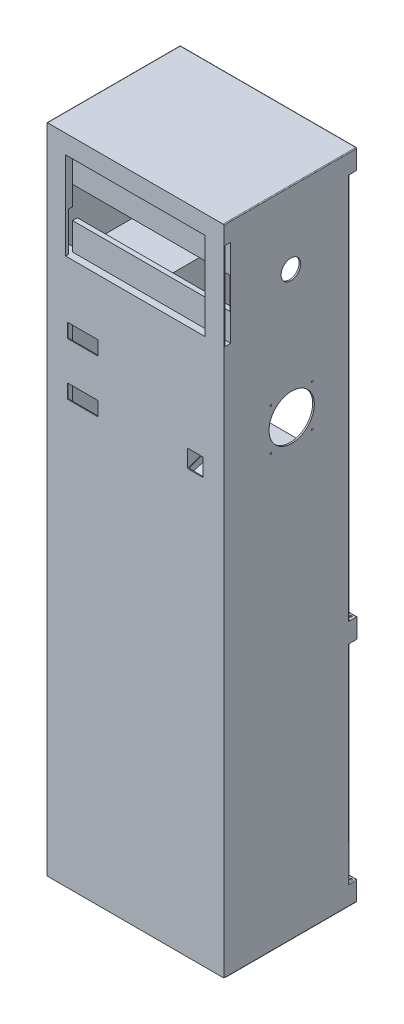
SolidWorks part; units mm, degrees
ref_plane "Front Plane" through (0, 0, 0) normal (0, 0, 1) x (1, 0, 0)
ref_plane "Top Plane" through (0, 0, 0) normal (0, 1, 0) x (1, 0, 0)
ref_plane "Right Plane" through (0, 0, 0) normal (1, 0, 0) x (0, 0, -1)
sketch "Sketch1" plane through (0, 0, 0) normal (0, 1, 0) x (1, 0, 0)
  line L1 (-225.5, 167.5) -> (225.5, 167.5)
  line L2 (-225.5, 167.5) -> (-225.5, -167.5)
  line L3 (-225.5, -167.5) -> (225.5, -167.5)
  line L4 (225.5, 167.5) -> (225.5, -167.5)
  line L5 (-225.5, 167.5) -> (225.5, -167.5) construction
  line L6 (-225.5, -167.5) -> (225.5, 167.5) construction
  point P0 (0, 0)
  dimension "D1" = 451
  dimension "D2" = 335
extrude "Boss-Extrude2" add sketch "Sketch1" along normal blind 1346
sketch "Sketch3" plane through (0, 0, -167.5) normal (0, 0, -1) x (-1, 0, 0)
  line L0 (225.5, 50) -> (225.5, 580)
  line L1 (225.5, 1346) -> (225.5, 0) construction
  line L2 (-225.5, 0) -> (225.5, 0) construction
  line L3 (225.5, 50) -> (-225.5, 50)
  line L4 (-225.5, 1346) -> (-225.5, 0) construction
  line L5 (-225.5, 50) -> (-225.5, 580)
  line L6 (-225.5, 580) -> (225.5, 580)
  line L7 (-225.5, 1346) -> (225.5, 1346) construction
  line L8 (225.5, 630) -> (-225.5, 630)
  line L9 (225.5, 630) -> (225.5, 1296)
  line L10 (225.5, 1296) -> (-225.5, 1296)
  line L11 (-225.5, 630) -> (-225.5, 1296)
  dimension "D1" = 530
  dimension "D2" = 50
  dimension "D3" = 50
  dimension "D4" = 50
fillet "Fillet1" radius 2 1 edges at (0, 0, -167.5)
sketch "Sketch6" plane through (0, 0, 167.5) normal (0, 0, 1) x (1, 0, 0)
  line L1 (-225.5, 1346) -> (225.5, 1346)
  line L2 (-225.5, 1346) -> (-225.5, 2)
  line L3 (-225.5, 2) -> (225.5, 2)
  line L4 (225.5, 1346) -> (225.5, 2)
extrude "Boss-Extrude3" add sketch "Sketch6" along normal blind 5
extrude "Cut-Extrude2" cut sketch "Sketch3" against normal blind 20
sketch "Sketch9" plane through (0, 0, -147.5) normal (0, 0, -1) x (-1, 0, 0)
  line L0 (-225.5, 50) -> (225.5, 50) construction
  line L1 (225.5, 580) -> (-225.5, 580) construction
  line L2 (-196.5, 50) -> (196.5, 50)
  line L3 (-196.5, 50) -> (-196.5, 580)
  line L4 (-196.5, 580) -> (196.5, 580)
  line L5 (196.5, 50) -> (196.5, 580)
  line L6 (-225.5, 580) -> (-225.5, 50) construction
  line L7 (225.5, 50) -> (225.5, 580) construction
  dimension "D1" = 29
  dimension "D2" = 29
sketch "Sketch10" plane through (0, 0, -147.5) normal (0, 0, -1) x (-1, 0, 0)
  line L0 (-225.5, 630) -> (225.5, 630) construction
  line L1 (-196.5, 630) -> (196.5, 630)
  line L2 (-196.5, 630) -> (-196.5, 1296)
  line L3 (-196.5, 1296) -> (196.5, 1296)
  line L4 (196.5, 630) -> (196.5, 1296)
  line L5 (225.5, 1296) -> (-225.5, 1296) construction
  line L6 (225.5, 630) -> (225.5, 1296) construction
  line L7 (-225.5, 1296) -> (-225.5, 630) construction
  dimension "D1" = 29
  dimension "D2" = 29
extrude "Cut-Extrude3" cut sketch "Sketch10" against normal blind 15
sketch "Sketch11" plane through (0, 0, -132.5) normal (0, 0, -1) x (-1, 0, 0)
  line L6 (68.5, 710) -> (-196.5, 710)
  line L15 (-196.5, 710) -> (-196.5, 964)
  line L16 (68.5, 710) -> (68.5, 964)
  line L17 (68.5, 964) -> (-196.5, 964)
  line L18 (-196.5, 1296) -> (-196.5, 981)
  line L19 (51.5, 1296) -> (-196.5, 1296)
  line L20 (51.5, 1296) -> (51.5, 981)
  line L21 (51.5, 981) -> (-196.5, 981)
  line L22 (68.5, 981) -> (196.5, 981)
  line L23 (196.5, 1296) -> (196.5, 981)
  line L24 (68.5, 1296) -> (68.5, 981)
  line L25 (68.5, 1296) -> (196.5, 1296)
  line L26 (-225.5, 630) -> (225.5, 630) construction
extrude "Cut-Extrude9" cut sketch "Sketch11" against normal blind 272
sketch "Sketch23" plane through (0, 981, 0) normal (0, 1, 0) x (1, 0, 0)
  line L0 (-68.5, -139.5) -> (-68.5, 132.5) construction
  line L1 (-68.5, 115.5) -> (-196.5, 115.5)
  line L2 (-68.5, 115.5) -> (-68.5, 112.5)
  line L3 (-68.5, 112.5) -> (-196.5, 112.5)
  line L4 (-196.5, 115.5) -> (-196.5, 112.5)
  line L5 (-196.5, -139.5) -> (-196.5, 132.5) construction
  line L6 (-68.5, 132.5) -> (-196.5, 132.5) construction
  line L7 (-51.5, -139.5) -> (-51.5, 132.5) construction
  line L8 (-51.5, 115.5) -> (196.5, 115.5)
  line L9 (-51.5, 115.5) -> (-51.5, 112.5)
  line L10 (-51.5, 112.5) -> (196.5, 112.5)
  line L11 (196.5, 115.5) -> (196.5, 112.5)
  line L12 (196.5, -139.5) -> (196.5, 132.5) construction
  line L13 (196.5, 132.5) -> (-51.5, 132.5) construction
  dimension "D1" = 17
  dimension "D2" = 3
  dimension "D3" = 3
  dimension "D4" = 17
extrude "Boss-Extrude4" add sketch "Sketch23" along normal blind 17
sketch "Sketch24" plane through (0, 1296, 0) normal (0, -1, 0) x (1, 0, 0)
  line L0 (-51.5, 139.5) -> (-51.5, -132.5) construction
  line L1 (-51.5, -115.5) -> (196.5, -115.5)
  line L2 (-51.5, -115.5) -> (-51.5, -112.5)
  line L3 (-51.5, -112.5) -> (196.5, -112.5)
  line L4 (196.5, -115.5) -> (196.5, -112.5)
  line L5 (196.5, 139.5) -> (196.5, -147.5) construction
  line L6 (-68.5, 139.5) -> (-68.5, -132.5) construction
  line L7 (-68.5, -115.5) -> (-196.5, -115.5)
  line L8 (-68.5, -115.5) -> (-68.5, -112.5)
  line L9 (-68.5, -112.5) -> (-196.5, -112.5)
  line L10 (-196.5, -115.5) -> (-196.5, -112.5)
  line L11 (-196.5, 139.5) -> (-196.5, -147.5) construction
  dimension "D1" = 17
  dimension "D2" = 3
  dimension "D3" = 17
  dimension "D4" = 3
extrude "Boss-Extrude5" add sketch "Sketch24" along normal blind 17
extrude "Cut-Extrude10" cut sketch "Sketch9" against normal blind 287
sketch "Sketch26" plane through (0, 981, 0) normal (0, 1, 0) x (1, 0, 0)
  line L1 (-196.5, 112.5) -> (-68.5, 112.5) construction
  line L2 (-196.5, -139.5) -> (-85.5, -139.5)
  line L3 (-196.5, -139.5) -> (-196.5, 112.5)
  line L4 (-196.5, 112.5) -> (-85.5, 112.5)
  line L5 (-85.5, -139.5) -> (-85.5, 112.5)
  line L6 (-68.5, -139.5) -> (-68.5, 112.5) construction
  dimension "D1" = 0
  dimension "D2" = 17
extrude "Cut-Extrude11" cut sketch "Sketch26" against normal up to surface (401 mm away) up to face at (0, 580, -80.75)
sketch "Sketch29" plane through (-196.5, 0, 0) normal (1, 0, 0) x (0, 0, -1)
  line L0 (112.5, 998) -> (112.5, 580) construction
  line L1 (-139.5, 1296) -> (112.5, 1296)
  line L2 (-139.5, 1296) -> (-139.5, 580)
  line L3 (-139.5, 580) -> (112.5, 580)
  line L4 (112.5, 1296) -> (112.5, 580)
  dimension "D1" = 0
extrude "Cut-Extrude12" cut sketch "Sketch29" against normal blind 27
sketch "Sketch33" plane through (0, 1296, 0) normal (0, -1, 0) x (1, 0, 0)
  line L1 (-223.5, 139.5) -> (-68.5, 139.5)
  line L2 (-223.5, 139.5) -> (-223.5, -112.5)
  line L3 (-223.5, -112.5) -> (-68.5, -112.5)
  line L4 (-68.5, 139.5) -> (-68.5, -112.5)
  dimension "D1" = 0
extrude "Cut-Extrude13" cut sketch "Sketch33" against normal blind 48
sketch "Sketch36" plane through (0, 0, 139.5) normal (0, 0, -1) x (-1, 0, 0)
  line L1 (-196.5, 1296) -> (51.5, 1296)
  line L2 (-196.5, 1296) -> (-196.5, 981)
  line L3 (-196.5, 981) -> (51.5, 981)
  line L4 (51.5, 1296) -> (51.5, 981)
extrude "Cut-Extrude14" cut sketch "Sketch36" against normal blind 31
sketch "Sketch39" plane through (0, 0, 139.5) normal (0, 0, -1) x (-1, 0, 0)
  line L0 (223.5, 1344) -> (223.5, 580) construction
  line L1 (68.5, 1344) -> (223.5, 1344)
  line L2 (68.5, 1344) -> (68.5, 981)
  line L3 (68.5, 981) -> (223.5, 981)
  line L4 (223.5, 1344) -> (223.5, 981)
  line L5 (68.5, 981) -> (85.5, 981) construction
  line L7 (223.5, 981) -> (85.5, 981)
  line L8 (223.5, 981) -> (223.5, 580)
  line L9 (223.5, 580) -> (85.5, 580)
  line L10 (85.5, 981) -> (85.5, 580)
  line M1 (223.5, 580) -> (223.5, 1344)
  line M2 (223.5, 1344) -> (68.5, 1344)
  line M3 (68.5, 1344) -> (68.5, 981)
  line M4 (68.5, 981) -> (85.5, 981)
  line M5 (85.5, 981) -> (85.5, 580)
  line M10 (196.5, 580) -> (223.5, 580)
  dimension "D1" = 0
extrude "Cut-Extrude15" cut sketch "Sketch39" against normal blind 31 contours L9 L3 M10 M1 M5 | L3 M4 M1 M2 M3
sketch "Sketch41" plane through (0, 0, 139.5) normal (0, 0, -1) x (-1, 0, 0)
  line L1 (-196.5, 964) -> (68.5, 964)
  line L2 (-196.5, 964) -> (-196.5, 710)
  line L3 (-196.5, 710) -> (68.5, 710)
  line L4 (68.5, 964) -> (68.5, 710)
extrude "Cut-Extrude16" cut sketch "Sketch41" against normal blind 31
sketch "Sketch43" plane through (0, 0, 170.5) normal (0, 0, -1) x (-1, 0, 0)
  line L0 (68.5, 1344) -> (68.5, 981) construction
  line L1 (81.5, 1294) -> (186.5, 1294)
  line L2 (81.5, 1294) -> (81.5, 1014)
  line L3 (81.5, 1014) -> (186.5, 1014)
  line L4 (186.5, 1294) -> (186.5, 1014)
  line L5 (223.5, 1344) -> (68.5, 1344) construction
  dimension "D1" = 13
  dimension "D2" = 50
  dimension "D3" = 105
  dimension "D4" = 280
extrude "Boss-Extrude6" add sketch "Sketch43" along normal blind 13.5
sketch "Sketch44" plane through (0, 0, 157) normal (0, 0, -1) x (-1, 0, 0)
  line L0 (186.5, 1294) -> (81.5, 1294) construction
  line L1 (92, 1280.25) -> (176, 1280.25)
  line L2 (92, 1280.25) -> (92, 1173.75)
  line L3 (92, 1173.75) -> (176, 1173.75)
  line L4 (176, 1280.25) -> (176, 1173.75)
  line L5 (92, 1146.25) -> (176, 1146.25)
  line L6 (186.5, 1014) -> (186.5, 1294) construction
  line L7 (81.5, 1160) -> (186.5, 1160)
  line L8 (81.5, 1294) -> (81.5, 1014) construction
  line L9 (186.5, 1014) -> (186.5, 1294) construction
  line L10 (176, 1039.75) -> (176, 1146.25)
  line L11 (92, 1039.75) -> (176, 1039.75)
  line L12 (92, 1039.75) -> (92, 1146.25)
  point P8 (134, 1173.75)
  dimension "D1" = 84
  dimension "D2" = 106.5
  dimension "D3" = 13.75
  dimension "D4" = 52.5
  dimension "D5" = 13.75
extrude "Cut-Extrude17" cut sketch "Sketch44" against normal blind 13.5 contours L4 L1 L2 L3 | L12 L11 L10 L5
sketch "Sketch46" plane through (0, 0, 139.5) normal (0, 0, -1) x (-1, 0, 0)
  line L5 (-196.5, 580) -> (196.5, 580)
  line L6 (-196.5, 580) -> (-196.5, 50)
  line L7 (-196.5, 50) -> (196.5, 50)
  line L8 (196.5, 580) -> (196.5, 50)
extrude "Cut-Extrude18" cut sketch "Sketch46" against normal blind 31
sketch "Sketch48" plane through (-196.5, 0, 0) normal (1, 0, 0) x (0, 0, -1)
  line L0 (-170.5, 50) -> (147.5, 50) construction
  line L1 (-170.5, 580) -> (112.5, 580)
  line L2 (-170.5, 580) -> (-170.5, 547)
  line L3 (-170.5, 547) -> (112.5, 547)
  line L4 (112.5, 580) -> (112.5, 547)
  dimension "D1" = 497
extrude "Boss-Extrude9" add sketch "Sketch48" along normal blind 31 separate body contours L2 L1 L4 L3
chamfer "Chamfer1" distance 30 angle 45 1 edges at (-165.5, 580, 29)
sketch "Sketch55" plane through (0, 50, 0) normal (0, 1, 0) x (1, 0, 0)
  line L1 (196.5, -170.5) -> (126.5, -170.5)
  line L2 (196.5, -170.5) -> (196.5, 147.5)
  line L3 (196.5, 147.5) -> (126.5, 147.5)
  line L4 (126.5, -170.5) -> (126.5, 147.5)
  line L5 (0, 95.2537) -> (0, -34.731)
  line L6 (-196.5, 147.5) -> (-126.5, 147.5)
  line L7 (-126.5, -170.5) -> (-126.5, 147.5)
  line L8 (-196.5, -170.5) -> (-126.5, -170.5)
  line L9 (-196.5, -170.5) -> (-196.5, 147.5)
  line M12 (-196.5, 147.5) -> (-196.5, -170.5)
  line M13 (-196.5, -170.5) -> (196.5, -170.5)
  line M14 (196.5, -170.5) -> (196.5, 147.5)
  dimension "D1" = 70
extrude "Cut-Extrude19" cut sketch "Sketch55" against normal blind 35 contours L7 L6 M13 M12 | L4 L3 M13 M14
sketch "Sketch56" plane through (0, 15, 0) normal (0, 1, 0) x (1, 0, 0)
  line L0 (-126.5, -170.5) -> (-126.5, 147.5) construction
  line L1 (0, -25.1133) -> (0, -98.0169)
  circle A0 centre (-161.5, 0) radius 17.5
  circle A1 centre (161.5, 0) radius 17.5
  dimension "D1" = 35
extrude "Cut-Extrude20" cut sketch "Sketch56" against normal blind 10 contours A0 | A1
sketch "Sketch57" plane through (0, 5, 0) normal (0, 1, 0) x (1, 0, 0)
  line L0 (0, 0) -> (0, 42.7914)
  circle A0 centre (161.5, 0) radius 4
  circle A1 centre (-161.5, 0) radius 4
  dimension "D1" = 8
extrude "Cut-Extrude21" cut sketch "Sketch57" against normal through all contours A0 | A1
sketch "Sketch58" plane through (0, 1346, 0) normal (0, 1, 0) x (1, 0, 0)
  line L1 (-225.5, 167.5) -> (225.5, 167.5)
  line L2 (-225.5, 167.5) -> (-225.5, -172.5)
  line L3 (-225.5, -172.5) -> (225.5, -172.5)
  line L4 (225.5, 167.5) -> (225.5, -172.5)
extrude "Boss-Extrude10" add sketch "Sketch58" along normal blind 319
sketch "Sketch59" plane through (0, 0, 172.5) normal (0, 0, 1) x (1, 0, 0)
  line L1 (-177.7, 1617.2) -> (177.7, 1617.2)
  line L2 (-177.7, 1617.2) -> (-177.7, 1393.8)
  line L3 (-177.7, 1393.8) -> (177.7, 1393.8)
  line L4 (177.7, 1617.2) -> (177.7, 1393.8)
  line L9 (-225.5, 1665) -> (225.5, 1665) construction
  line L10 (225.5, 2) -> (225.5, 1665) construction
  line L11 (-225.5, 1665) -> (-225.5, 2) construction
  dimension "D1" = 47.8
  dimension "D2" = 47.8
  dimension "D3" = 47.8
  dimension "D4" = 223.4
extrude "Cut-Extrude22" cut sketch "Sketch59" against normal blind 17.7
sketch "Sketch60" plane through (177.7, 0, 0) normal (-1, 0, 0) x (0, 0, 1)
  line L0 (154.8, 1393.8) -> (172.5, 1393.8) construction
  line L1 (154.8, 1617.2) -> (169.6, 1617.2)
  line L2 (154.8, 1617.2) -> (154.8, 1393.8)
  line L3 (154.8, 1393.8) -> (169.6, 1393.8)
  line L4 (169.6, 1617.2) -> (169.6, 1393.8)
  dimension "D1" = 14.8
extrude "Cut-Extrude23" cut sketch "Sketch60" against normal up to surface (47.8 mm away) up to face at (225.5, 563.1724, -72.0609)
sketch "Sketch61" plane through (0, 1296, 0) normal (0, -1, 0) x (1, 0, 0)
  line L0 (-225.5, -147.5) -> (-225.5, -167.5) construction
  line L2 (-225.5, -167.5) -> (225.5, -167.5) construction
  circle A0 centre (-217.5, -159.5) radius 2.5
  dimension "D1" = 5
  dimension "D2" = 8
  dimension "D3" = 8
extrude "Cut-Extrude24" cut sketch "Sketch61" against normal blind 10
sketch "Sketch62" plane through (0, 630, 0) normal (0, 1, 0) x (1, 0, 0)
  line L0 (225.5, 167.5) -> (-225.5, 167.5) construction
  line L1 (-225.5, 147.5) -> (-225.5, 167.5) construction
  circle A0 centre (-217.5, 159.5) radius 3.4591
  dimension "D1" = 8
  dimension "D2" = 8
sketch "Sketch63" plane through (0, 580, 0) normal (0, -1, 0) x (1, 0, 0)
  line L0 (-225.5, -147.5) -> (-225.5, -167.5) construction
  line L1 (-225.5, -167.5) -> (225.5, -167.5) construction
  circle A0 centre (-217.5, -159.5) radius 2.5
  dimension "D1" = 5
  dimension "D2" = 8
  dimension "D3" = 8
sketch "Sketch64" plane through (0, 50, 0) normal (0, 1, 0) x (1, 0, 0)
  line L0 (225.5, 167.5) -> (-225.5, 167.5) construction
  line L1 (-225.5, 147.5) -> (-225.5, 167.5) construction
  circle A0 centre (-217.5, 159.5) radius 2.5
  dimension "D1" = 5
  dimension "D2" = 8
  dimension "D3" = 8
sketch "Sketch66" plane through (0, 0, 170.5) normal (0, 0, -1) x (-1, 0, 0)
  line L0 (176, 1280.25) -> (176, 1173.75) construction
  line L1 (95, 1250.25) -> (173, 1250.25)
  line L2 (95, 1250.25) -> (95, 1214.25)
  line L3 (95, 1214.25) -> (173, 1214.25)
  line L4 (173, 1250.25) -> (173, 1214.25)
  line L5 (92, 1280.25) -> (92, 1173.75) construction
  line L6 (92, 1280.25) -> (176, 1280.25) construction
  line L7 (92, 1173.75) -> (176, 1173.75) construction
  line L8 (95, 1116.25) -> (95, 1080.25)
  line L9 (173, 1116.25) -> (173, 1080.25)
  line L10 (95, 1080.25) -> (173, 1080.25)
  line L11 (95, 1116.25) -> (173, 1116.25)
  dimension "D1" = 3
  dimension "D2" = 3
  dimension "D3" = 30
  dimension "D4" = 40.5
extrude "Cut-Extrude28" cut sketch "Sketch66" against normal through all
fillet "Fillet2" radius 2 24 edges at (-225.5, 0, 1) (-225.5, 0.5858, -166.9142) (225.5, 0.5858, -166.9142) (196.5, 315, -147.5) (-196.5, 315, -147.5) (225.5, 1, 167.5) (-225.5, 1, 167.5) (-225.5, 1665, 2.5) (225.5, 1665, 2.5) (0, 1665, -167.5) (-225.5, 50, -157.5) (225.5, 315, -147.5) (225.5, 50, -157.5) (-225.5, 315, -147.5) (0, 50, -167.5) (0, 580, -167.5) (-225.5, 963, -147.5) (225.5, 963, -147.5) (225.5, 1296, -157.5) (0, 1296, -167.5) (0, 630, -167.5) (225.5, 0, 1) (196.5, 963, -147.5) (-196.5, 963, -147.5)
sketch "Sketch67" plane through (0, 0, 172.5) normal (0, 0, 1) x (1, 0, 0)
  line L0 (225.5, 2) -> (225.5, 1663) construction
  line L1 (133, 1080.25) -> (173, 1080.25)
  line L2 (133, 1080.25) -> (133, 1125.25)
  line L3 (133, 1125.25) -> (173, 1125.25)
  line L4 (173, 1080.25) -> (173, 1125.25)
  dimension "D1" = 45
  dimension "D2" = 52.5
  dimension "D3" = 40
extrude "Cut-Extrude29" cut sketch "Sketch67" against normal blind 10
sketch "Sketch68" plane through (173, 0, 0) normal (-1, 0, 0) x (0, 0, 1)
  line L0 (172.5, 1080.25) -> (107.5, 1102.75)
  line L3 (172.5, 1080.25) -> (107.5, 1080.25)
  line L4 (107.5, 1102.75) -> (107.5, 1080.25)
extrude "Boss-Extrude11" add sketch "Sketch68" along normal up to surface (40 mm away) up to face at (133, 1102.75, 171.5)
sketch "Sketch69" plane through (0, 0, 107.5) normal (0, 0, -1) x (-1, 0, 0)
  line L0 (-133, 1080.9423) -> (-133, 1125.25) construction
  line L1 (-131, 1078.25) -> (-175, 1078.25)
  line L2 (-131, 1078.25) -> (-131, 1127.25)
  line L3 (-131, 1127.25) -> (-175, 1127.25)
  line L4 (-175, 1078.25) -> (-175, 1127.25)
  line L5 (-173, 1125.25) -> (-173, 1080.9423) construction
  line L6 (-133, 1125.25) -> (-173, 1125.25) construction
  line L7 (-173, 1080.25) -> (-133, 1080.25) construction
  line L9 (-131, 1078.25) -> (-133, 1078.25)
  line L10 (-131, 1078.25) -> (-131, 1127.25)
  line L11 (-131, 1127.25) -> (-133, 1127.25)
  line L12 (-133, 1078.25) -> (-133, 1127.25)
  line L13 (-175, 1127.25) -> (-131, 1127.25)
  line L14 (-175, 1127.25) -> (-175, 1125.25)
  line L15 (-175, 1125.25) -> (-131, 1125.25)
  line L16 (-131, 1127.25) -> (-131, 1125.25)
  line L17 (-175, 1127.25) -> (-173, 1127.25)
  line L18 (-175, 1127.25) -> (-175, 1078.25)
  line L19 (-175, 1078.25) -> (-173, 1078.25)
  line L20 (-173, 1127.25) -> (-173, 1078.25)
  line L21 (-175, 1078.25) -> (-131, 1078.25)
  line L22 (-175, 1078.25) -> (-175, 1080.25)
  line L23 (-175, 1080.25) -> (-131, 1080.25)
  line L24 (-131, 1078.25) -> (-131, 1080.25)
  line M11 (-133, 1080.25) -> (-133, 1102.75)
  line M13 (-173, 1102.75) -> (-173, 1080.25)
  dimension "D1" = 2
  dimension "D2" = 2
  dimension "D3" = 2
  dimension "D4" = 2
  dimension "D5" = 2
  dimension "D6" = 2
  dimension "D7" = 2
  dimension "D8" = 2
extrude "Boss-Extrude12" add sketch "Sketch69" against normal through all contours L23 L10 L15 L12 M11 | L12 L15 L10 L3 | L3 L20 L15 L12 | L20 L13 L4 L15 | L18 L23 L20 L15 M13 | L23 L4 L1 L20 | L23 L12 L1 L2
sketch "Sketch70" plane through (0, 0, 107.5) normal (0, 0, -1) x (-1, 0, 0)
  line L1 (-173, 1080.25) -> (-133, 1080.25)
  line L2 (-173, 1080.25) -> (-173, 1078.25)
  line L3 (-173, 1078.25) -> (-133, 1078.25)
  line L4 (-133, 1080.25) -> (-133, 1078.25)
extrude "Boss-Extrude13" add sketch "Sketch70" against normal through all
sketch "Sketch71" plane through (0, 0, 107.5) normal (0, 0, -1) x (-1, 0, 0)
  line L1 (-131, 1078.25) -> (-175, 1078.25)
  line L2 (-131, 1078.25) -> (-131, 1127.25)
  line L3 (-131, 1127.25) -> (-175, 1127.25)
  line L4 (-175, 1078.25) -> (-175, 1127.25)
extrude "Boss-Extrude14" add sketch "Sketch71" along normal blind 2
sketch "Sketch72" plane through (0, 1017.9841, 352.3791) normal (0, 0.945, 0.3271) x (1, 0, 0)
  line L0 (133, 190.3511) -> (173, 190.3511) construction
  line L5 (134.75, 257.2411) -> (171.25, 257.2411)
  line L6 (134.75, 257.2411) -> (134.75, 192.2411)
  line L7 (134.75, 192.2411) -> (171.25, 192.2411)
  line L8 (171.25, 257.2411) -> (171.25, 192.2411)
  line L9 (134.75, 257.2411) -> (171.25, 192.2411) construction
  line L10 (134.75, 192.2411) -> (171.25, 257.2411) construction
  line L11 (173, 190.3511) -> (173, 259.1352) construction
  point P0 (153, 224.7411)
  dimension "D1" = 36.5
  dimension "D2" = 65
  dimension "D3" = 34.39
  dimension "D4" = 20
sketch "Sketch73" plane through (0, 1078.25, 0) normal (0, -1, 0) x (1, 0, 0)
  line L1 (175, 170.5) -> (131, 170.5)
  line L2 (175, 170.5) -> (175, 105.5)
  line L3 (175, 105.5) -> (131, 105.5)
  line L4 (131, 170.5) -> (131, 105.5)
extrude "Boss-Extrude15" add sketch "Sketch73" along normal blind 16
sketch "Sketch74" plane through (0, 0, 105.5) normal (0, 0, -1) x (-1, 0, 0)
  line L1 (-175, 1127.25) -> (-131, 1127.25)
  line L2 (-175, 1127.25) -> (-175, 1062.25)
  line L3 (-175, 1062.25) -> (-131, 1062.25)
  line L4 (-131, 1127.25) -> (-131, 1062.25)
extrude "Boss-Extrude16" add sketch "Sketch74" along normal blind 20
extrude "Cut-Extrude32" cut sketch "Sketch72" against normal blind 16
sketch "Sketch75" plane through (0, 84.1463, -243.0892) normal (0, -0.3271, 0.945) x (1, 0, 0)
  line L0 (171.25, 1077.2478) -> (134.75, 1077.2478) construction
  line L1 (171.25, 1061.2478) -> (171.25, 1077.2478) construction
  circle A0 centre (153, 1069.2478) radius 3.5
  dimension "D1" = 8
  dimension "D2" = 18.25
extrude "Cut-Extrude33" cut sketch "Sketch75" against normal through all
sketch "Sketch76" plane through (0, 84.1463, -243.0892) normal (0, -0.3271, 0.945) x (1, 0, 0)
  line L0 (171.25, 1077.2478) -> (134.75, 1077.2478) construction
  line L1 (141, 1074.7478) -> (165, 1074.7478)
  line L2 (141, 1074.7478) -> (141, 1063.7478)
  line L3 (141, 1063.7478) -> (165, 1063.7478)
  line L4 (165, 1074.7478) -> (165, 1063.7478)
  line L6 (134.75, 1061.2478) -> (134.75, 1077.2478) construction
  dimension "D1" = 24
  dimension "D2" = 11
  dimension "D3" = 2.5
  dimension "D4" = 6.25
extrude "Cut-Extrude34" cut sketch "Sketch76" against normal through all
sketch "Sketch77" plane through (-68.5, 0, 0) normal (-1, 0, 0) x (0, 0, 1)
  line L0 (-112.5, 1344) -> (170.5, 1344) construction
  circle A0 centre (109.6933, 1184) radius 20
  dimension "D1" = 40
  dimension "D2" = 160
extrude "Cut-Extrude35" cut sketch "Sketch77" against normal up to surface (17 mm away) up to face at (-51.5, 1138.5, -69.6667)
sketch "Sketch78" plane through (0, 981, 0) normal (0, 1, 0) x (1, 0, 0)
  line L0 (196.5, -170.5) -> (-51.5, -170.5) construction
  line L1 (-51.5, -170.5) -> (-51.5, 112.5) construction
  circle A0 centre (-36.5, -155.5) radius 7.5
  dimension "D1" = 15
  dimension "D2" = 15
  dimension "D3" = 15
extrude "Cut-Extrude36" cut sketch "Sketch78" against normal up to surface (17 mm away) up to face at (64, 964, 19)
sketch "Sketch79" plane through (0, 0, -167.5) normal (0, 0, -1) x (-1, 0, 0)
  line L0 (-225.5, 630) -> (225.5, 630) construction
  line L1 (-201.5, 625) -> (-56, 625)
  line L2 (-201.5, 625) -> (-201.5, 585)
  line L3 (-201.5, 585) -> (-56, 585)
  line L4 (-56, 625) -> (-56, 585)
  line L5 (-225.5, 628) -> (-225.5, 582) construction
  dimension "D1" = 40
  dimension "D2" = 5
  dimension "D3" = 145.5
  dimension "D4" = 24
extrude "Cut-Extrude37" cut sketch "Sketch79" against normal blind 16
sketch "Sketch82" plane through (225.5, 0, 0) normal (1, 0, 0) x (0, 0, -1)
  line L0 (-172.5, 1665) -> (165.5, 1665) construction
  line L1 (-172.5, 2) -> (-172.5, 1663) construction
  circle A0 centre (0.5, 1153) radius 57.705
  dimension "D1" = 115.41
  dimension "D2" = 512
  dimension "D3" = 173
sketch "Sketch83" plane through (225.5, 0, 0) normal (1, 0, 0) x (0, 0, -1)
  line L0 (147.5, 1296) -> (147.5, 630) construction
  line L1 (0, 1169.2244) -> (0, 1136.3498)
  line L2 (0, 1152.7871) -> (23.0061, 1152.7871)
  circle A0 centre (53, 1205.7202) radius 2.3
  circle A1 centre (-53, 1205.7202) radius 2.3
  circle A2 centre (53, 1099.854) radius 2.3
  circle A3 centre (-53, 1099.854) radius 2.3
  dimension "D1" = 94.5
sketch "Sketch84" plane through (0, 0, 157) normal (0, 0, -1) x (-1, 0, 0)
  line L0 (81.5, 1014) -> (186.5, 1014) construction
  line L1 (81.5, 1294) -> (81.5, 1014) construction
  line L2 (81.5, 1294) -> (81.5, 1014) construction
  line L3 (134, 1039.75) -> (134, 1027.8788)
  line L4 (92, 1039.75) -> (176, 1039.75) construction
  line L5 (92, 1093) -> (116.7511, 1093)
  line L6 (92, 1039.75) -> (92, 1146.25) construction
  line L8 (112.9928, 1168.6) -> (144.1417, 1168.6)
  circle A0 centre (107.5, 1034.6) radius 3
  circle A1 centre (92.5, 1034.6) radius 3
  circle A2 centre (107.5, 1151.4) radius 3
  circle A3 centre (92.5, 1151.4) radius 3
  circle A4 centre (160.5, 1034.6) radius 3
  circle A5 centre (175.5, 1034.6) radius 3
  circle A6 centre (175.5, 1151.4) radius 3
  circle A7 centre (160.5, 1151.4) radius 3
  circle A8 centre (160.5, 1285.4) radius 3
  circle A9 centre (175.5, 1168.6) radius 3
  circle A10 centre (107.5, 1168.6) radius 3
  circle A11 centre (160.5, 1168.6) radius 3
  circle A12 centre (92.5, 1285.4) radius 3
  circle A13 centre (92.5, 1168.6) radius 3
  circle A14 centre (175.5, 1285.4) radius 3
  circle A15 centre (107.5, 1285.4) radius 3
  dimension "D1" = 20.6
  dimension "D3" = 11
  dimension "D2" = 26
extrude "Cut-Extrude40" cut sketch "Sketch84" against normal blind 10 contours A12 | A15 | A9 | A11 | A7 | A6 | A13 | A8 | A14 | A10 | A2 | A3 | A5 | A4 | A0 | A1
sketch "Sketch85" plane through (0, 580, 0) normal (0, -1, 0) x (1, 0, 0)
  line L1 (-85.5, -112.5) -> (196.5, -112.5)
  line L2 (-85.5, -112.5) -> (-85.5, 170.5)
  line L3 (-85.5, 170.5) -> (196.5, 170.5)
  line L4 (196.5, -112.5) -> (196.5, 170.5)
extrude "Cut-Extrude41" cut sketch "Sketch85" against normal up to surface (50 mm away) up to face at (0, 630, -147.4714)
sketch "Sketch86" plane through (0, 630, 0) normal (0, 1, 0) x (1, 0, 0)
  line L1 (225.5, 145.5) -> (225.5, 165.5) construction
  line L2 (223.5, 147.5) -> (198.5, 147.5) construction
  circle A0 centre (150.5, 152.5) radius 3
  dimension "D1" = 5
  dimension "D2" = 75
sketch "Sketch87" plane through (0, 50, 0) normal (0, 1, 0) x (1, 0, 0)
  line L0 (223.5, 147.5) -> (198.5, 147.5) construction
  line L1 (225.5, 165.5) -> (225.5, 145.5) construction
  circle A0 centre (150.5, 152.5) radius 3
  dimension "D1" = 5
  dimension "D2" = 75
sketch "Sketch90" plane through (0, 0, -132.5) normal (0, 0, -1) x (-1, 0, 0)
  line L0 (-196.5, 710) -> (-196.5, 630) construction
  line L1 (-196.5, 633) -> (68.5, 633)
  line L2 (-196.5, 633) -> (-196.5, 695)
  line L3 (-196.5, 695) -> (68.5, 695)
  line L4 (68.5, 633) -> (68.5, 695)
  line L5 (-196.5, 710) -> (68.5, 710) construction
  line L6 (-196.5, 630) -> (196.5, 630) construction
  dimension "D1" = 15
  dimension "D2" = 3
extrude "Cut-Extrude47" cut sketch "Sketch90" against normal up to surface (303 mm away) up to face at (64, 837, 170.5)
sketch "Sketch92" plane through (0, 981, 0) normal (0, 1, 0) x (1, 0, 0)
  circle A0 centre (-36.5, -155.5) radius 7.5
extrude "Cut-Extrude48" cut sketch "Sketch92" against normal up to surface (351 mm away) up to face at (55.5, 630, 29)
sketch "Sketch94" plane through (0, 0, -167.5) normal (0, 0, -1) x (-1, 0, 0)
  line L0 (-225.5, 1298) -> (-225.5, 1663) construction
  line L1 (-225.5, 1615) -> (225.5, 1615)
  line L2 (-225.5, 1615) -> (-225.5, 1346)
  line L3 (-225.5, 1346) -> (225.5, 1346)
  line L4 (225.5, 1615) -> (225.5, 1346)
  line L5 (225.5, 1663) -> (225.5, 1296) construction
  line L6 (225.5, 1296) -> (-223.5, 1296) construction
  line L7 (-223.5, 1665) -> (223.5, 1665) construction
  dimension "D1" = 50
  dimension "D2" = 50
extrude "Cut-Extrude49" cut sketch "Sketch94" against normal up to surface (20 mm away) up to face at (211, 963, -147.5)
sketch "Sketch95" plane through (0, 0, -147.5) normal (0, 0, -1) x (-1, 0, 0)
  line L0 (225.5, 1346) -> (-225.5, 1346) construction
  line L1 (-196.5, 1346) -> (198.5, 1346)
  line L2 (-196.5, 1346) -> (-196.5, 1615)
  line L3 (-196.5, 1615) -> (198.5, 1615)
  line L4 (198.5, 1346) -> (198.5, 1615)
  line L5 (-225.5, 1615) -> (225.5, 1615) construction
  dimension "D1" = 0
  dimension "D2" = 0
extrude "Cut-Extrude50" cut sketch "Sketch95" against normal blind 290
sketch "Sketch96" plane through (-177.7, 0, 0) normal (1, 0, 0) x (0, 0, -1)
  line L1 (-154.8, 1393.8) -> (-164.8, 1393.8)
  line L2 (-154.8, 1393.8) -> (-154.8, 1493.8)
  line L3 (-154.8, 1493.8) -> (-164.8, 1493.8)
  line L4 (-164.8, 1393.8) -> (-164.8, 1493.8)
  dimension "D1" = 100
  dimension "D2" = 10
extrude "Cut-Extrude51" cut sketch "Sketch96" against normal blind 45.8
sketch "Sketch97" plane through (0, 0, 154.8) normal (0, 0, 1) x (1, 0, 0)
  line L0 (-223.5, 1393.8) -> (225.5, 1393.8) construction
  line L1 (-223.5, 1493.8) -> (-177.7, 1493.8)
  line L2 (-223.5, 1493.8) -> (-223.5, 1393.8)
  line L3 (-223.5, 1393.8) -> (-177.7, 1393.8)
  line L4 (-177.7, 1493.8) -> (-177.7, 1393.8)
extrude "Cut-Extrude52" cut sketch "Sketch97" against normal blind 45.8
sketch "Sketch99" plane through (-198.5, 0, 0) normal (1, 0, 0) x (0, 0, -1)
  line L0 (-142.5, 1346) -> (147.5, 1346) construction
  line L1 (-142.5, 1615) -> (115.5, 1615)
  line L2 (-142.5, 1615) -> (-142.5, 1346)
  line L3 (-142.5, 1346) -> (115.5, 1346)
  line L4 (115.5, 1615) -> (115.5, 1346)
  line L5 (147.5, 1346) -> (147.5, 1615) construction
  dimension "D1" = 0
  dimension "D2" = 32
extrude "Cut-Extrude54" cut sketch "Sketch99" against normal blind 25
sketch "Sketch101" plane through (196.5, 0, 0) normal (-1, 0, 0) x (0, 0, 1)
  line L0 (142.5, 1346) -> (-147.5, 1346) construction
  line L1 (142.5, 1615) -> (-115.5, 1615)
  line L2 (142.5, 1615) -> (142.5, 1346)
  line L3 (142.5, 1346) -> (-115.5, 1346)
  line L4 (-115.5, 1615) -> (-115.5, 1346)
  line L5 (-147.5, 1615) -> (-147.5, 1346) construction
  dimension "D1" = 32
extrude "Cut-Extrude55" cut sketch "Sketch101" against normal blind 25
sketch "Sketch103" plane through (0, 1346, 0) normal (0, 1, 0) x (1, 0, 0)
  line L0 (221.5, -142.5) -> (-223.5, -142.5) construction
  line L1 (-223.5, -142.5) -> (-223.5, 115.5) construction
  circle A0 centre (-8.5, -92.5) radius 15
  dimension "D1" = 30
  dimension "D2" = 50
  dimension "D3" = 215
extrude "Cut-Extrude56" cut sketch "Sketch103" against normal up to surface (50 mm away) up to face at (72.5, 1296, 29)
sketch "Sketch105" plane through (0, 1615, 0) normal (0, -1, 0) x (1, 0, 0)
  line L0 (225.5, -147.5) -> (225.5, -165.5) construction
  line L1 (225.5, -147.5) -> (196.5, -147.5) construction
  circle A0 centre (187.5, -152.5) radius 3
  dimension "D1" = 38
  dimension "D2" = 5
sketch "Sketch106" plane through (0, 1296, 0) normal (0, -1, 0) x (1, 0, 0)
  line L0 (225.5, -145.5) -> (225.5, -165.5) construction
  line L1 (198.5, -147.5) -> (223.5, -147.5) construction
  circle A0 centre (187.5, -152.5) radius 3
  dimension "D1" = 6
  dimension "D2" = 38
  dimension "D3" = 5
extrude "Cut-Extrude58" cut sketch "Sketch106" against normal blind 19
sketch "Sketch109" plane through (0, 580, 0) normal (0, -1, 0) x (1, 0, 0)
  line L0 (198.5, -147.5) -> (223.5, -147.5) construction
  line L1 (225.5, -145.5) -> (225.5, -165.5) construction
  circle A0 centre (187.5, -152.5) radius 3
  dimension "D1" = 5
  dimension "D2" = 38
sketch "Sketch110" plane through (0, 1346, 0) normal (0, 1, 0) x (1, 0, 0)
  line L0 (225.5, 147.5) -> (225.5, 165.5) construction
  line L1 (196.5, 147.5) -> (225.5, 147.5) construction
  circle A0 centre (150.5, 152.5) radius 3
  dimension "D1" = 6
  dimension "D2" = 75
  dimension "D3" = 5
extrude "Cut-Extrude61" cut sketch "Sketch110" against normal blind 19
sketch "Sketch111" plane through (0, 1346, 0) normal (0, 1, 0) x (1, 0, 0)
  line L0 (223.5, 167.5) -> (-223.5, 167.5) construction
  line L1 (-225.5, 147.5) -> (-225.5, 165.5) construction
  circle A0 centre (-217.5, 159.5) radius 2.5
  dimension "D1" = 8
  dimension "D2" = 8
extrude "Cut-Extrude62" cut sketch "Sketch111" against normal blind 10
sketch "Sketch112" plane through (0, 1615, 0) normal (0, -1, 0) x (1, 0, 0)
  line L0 (-223.5, -167.5) -> (223.5, -167.5) construction
  line L1 (-225.5, -147.5) -> (-225.5, -165.5) construction
  circle A0 centre (-217.5, -159.5) radius 2.5
  dimension "D1" = 5
  dimension "D2" = 8
  dimension "D3" = 8
fillet "Fillet3" radius 2 4 edges at (225.5, 1480.5, -147.5) (196.5, 1480.5, -147.5) (-198.5, 1480.5, -147.5) (-225.5, 1480.5, -147.5)
sketch "Sketch113" plane through (0, 0, -147.5) normal (0, 0, -1) x (-1, 0, 0)
  line L11 (0, 886) -> (0, 833.4541)
  line L12 (196.5, 240) -> (199.5, 240)
  line L13 (199.5, 240) -> (199.5, 218)
  line L14 (196.5, 240) -> (196.5, 218)
  line L15 (196.5, 218) -> (199.5, 218)
  line L16 (196.5, 864) -> (199.5, 864)
  line L17 (199.5, 886) -> (199.5, 864)
  line L18 (196.5, 886) -> (199.5, 886)
  line L19 (196.5, 886) -> (196.5, 864)
extrude "Boss-Extrude18" add sketch "Sketch113" along normal blind 35 contours L14 L15 L13 L12 | L17 L16 L19 L18
sketch "Sketch118" plane through (0, 0, -167.5) normal (0, 0, -1) x (-1, 0, 0)
  line L1 (225.5, 1296) -> (-225.5, 1296)
  line L2 (225.5, 1296) -> (225.5, 1346)
  line L3 (225.5, 1346) -> (-225.5, 1346)
  line L4 (-225.5, 1296) -> (-225.5, 1346)
extrude "Cut-Extrude65" cut sketch "Sketch118" against normal up to surface (20 mm away) up to face at (-212, 1480.5, -147.5)
sketch "Sketch120" plane through (0, 1296, 0) normal (0, -1, 0) x (1, 0, 0)
  line L0 (-198.5, -147.5) -> (198.5, -147.5) construction
  line L1 (-51.5, 170.5) -> (196.5, 170.5)
  line L2 (-51.5, 170.5) -> (-51.5, -147.5)
  line L3 (-51.5, -147.5) -> (196.5, -147.5)
  line L4 (196.5, 170.5) -> (196.5, -147.5)
extrude "Cut-Extrude68" cut sketch "Sketch120" against normal up to surface (50 mm away) up to face at (-224.9714, 1346, -146.9714)
sketch "Sketch122" plane through (0, 1296, 0) normal (0, 1, 0) x (1, 0, 0)
  line L1 (-51.5, 115.5) -> (196.5, 115.5)
  line L2 (-51.5, 115.5) -> (-51.5, 112.5)
  line L3 (-51.5, 112.5) -> (196.5, 112.5)
  line L4 (196.5, 115.5) -> (196.5, 112.5)
extrude "Cut-Extrude75" cut sketch "Sketch122" against normal up to surface (17 mm away) up to face at (72.5, 1279, -114)
sketch "Sketch125" plane through (0, 998, 0) normal (0, 1, 0) x (1, 0, 0)
  line L1 (196.5, 115.5) -> (-51.5, 115.5)
  line L2 (196.5, 115.5) -> (196.5, 112.5)
  line L3 (196.5, 112.5) -> (-51.5, 112.5)
  line L4 (-51.5, 115.5) -> (-51.5, 112.5)
extrude "Cut-Extrude80" cut sketch "Sketch125" against normal up to surface (17 mm away) up to face at (72.5, 981, -124)
sketch "Sketch126" plane through (0, 1346, 0) normal (0, 1, 0) x (1, 0, 0)
  line L1 (221.5, -142.5) -> (196.5, -142.5)
  line L2 (221.5, -142.5) -> (221.5, 115.5)
  line L3 (221.5, 115.5) -> (196.5, 115.5)
  line L4 (196.5, -142.5) -> (196.5, 115.5)
extrude "Cut-Extrude84" cut sketch "Sketch126" against normal up to surface (713 mm away) up to face at (-36.5, 633, 148)
fillet "Fillet4" radius 2 16 edges at (224.9142, 1296.5858, -147.5) (225.5, 1322, -147.5) (224.5, 1346, -147.5) (197.5, 1346, -147.5) (-224.5, 1346, -147.5) (-225.5, 1321, -147.5) (-224.5, 1296, -147.5) (197.5, 1296, -147.5) (196.5, 1296, -146.5) (196.5, 1346, -146.5) (196.5, 1321, -147.5) (225.5, 1298, -146.5) (-225.5, 1296, -146.5) (224.9142, 1296.5858, -146.9142) (225.5, 1346, -146.5) (-225.5, 1346, -146.5)
sketch "Sketch128" plane through (225.5, 0, 0) normal (1, 0, 0) x (0, 0, -1)
  line L0 (-172.5, 1665) -> (165.5, 1665) construction
  line L1 (-90.5, 1290) -> (63.5, 1290)
  line L2 (-93.5, 1287) -> (-93.5, 1023)
  line L3 (-90.5, 1020) -> (63.5, 1020)
  line L4 (66.5, 1287) -> (66.5, 1023)
  line L5 (-172.5, 2) -> (-172.5, 1663) construction
  line L6 (147.5, 1298) -> (147.5, 630) construction
  line L7 (165.5, 0) -> (-167.5, 0) construction
  line L8 (-13.5, 1266.9501) -> (-13.5, 1228.8313)
  line L9 (-75.2353, 1155) -> (-36.7762, 1155)
  circle A0 centre (54.5, 1278) radius 4
  circle A1 centre (-81.5, 1278) radius 4
  circle A2 centre (54.5, 1032) radius 4
  circle A3 centre (-81.5, 1032) radius 4
  arc A4 (-90.5, 1020) -> (-93.5, 1023) centre (-90.5, 1023) cw
  arc A5 (63.5, 1020) -> (66.5, 1023) centre (63.5, 1023) ccw
  arc A6 (-90.5, 1290) -> (-93.5, 1287) centre (-90.5, 1287) ccw
  arc A7 (63.5, 1290) -> (66.5, 1287) centre (63.5, 1287) cw
  dimension "D5" = 8
  dimension "D8" = 3
  dimension "D1" = 375
  dimension "D2" = 79
  dimension "D3" = 81
  dimension "D4" = 1020
  dimension "D6" = 12
  dimension "D7" = 12
sketch "Sketch130" plane through (221.5, 0, 0) normal (-1, 0, 0) x (0, 0, 1)
  line L0 (-147.5, 630) -> (-147.5, 1296) construction
  line L1 (-69.5, 1013.5602) -> (96.5, 1013.5602)
  line L2 (-69.5, 1013.5602) -> (-69.5, 1293)
  line L3 (-69.5, 1293) -> (96.5, 1293)
  line L4 (96.5, 1013.5602) -> (96.5, 1293)
  line L5 (172.5, 1665) -> (-165.5, 1665) construction
  line L6 (172.5, 2) -> (172.5, 1663) construction
  dimension "D1" = 78
  dimension "D2" = 372
  dimension "D3" = 76
extrude "Cut-Extrude85" cut sketch "Sketch82" against normal up to surface (29 mm away) up to face at (196.5, 837, 156.5)
extrude "Cut-Extrude86" cut sketch "Sketch83" against normal up to surface (29 mm away) contours A0 | A2 | A3 | A1 up to face at (196.5, 837, 156.5)
sketch "Sketch131" plane through (-223.5, 0, 0) normal (1, 0, 0) x (0, 0, -1)
  line L3 (115.5, 1615) -> (-142.5, 1615) construction
  line L4 (167.5, 1615) -> (167.5, 1663) construction
  circle A2 centre (-1.5, 1480.5) radius 1
  circle A4 centre (6.5, 1480.5) radius 1
  circle A5 centre (10.5, 1480.5) radius 1
  circle A6 centre (14.5, 1480.5) radius 1
  circle A7 centre (18.5, 1480.5) radius 1
  circle A8 centre (2.2299, 1479.055) radius 1
  circle A9 centre (5.9598, 1477.6101) radius 1
  circle A10 centre (9.6897, 1476.1651) radius 1
  circle A11 centre (13.4196, 1474.7201) radius 1
  circle A12 centre (17.1494, 1473.2752) radius 1
  circle A14 centre (4.4121, 1475.1104) radius 1
  circle A15 centre (7.3681, 1472.4157) radius 1
  circle A16 centre (10.3241, 1469.7209) radius 1
  circle A17 centre (13.2802, 1467.0261) radius 1
  circle A18 centre (0.283, 1476.9193) radius 1
  circle A19 centre (2.0659, 1473.3387) radius 1
  circle A20 centre (3.8489, 1469.758) radius 1
  circle A21 centre (5.6318, 1466.1774) radius 1
  circle A22 centre (7.4148, 1462.5967) radius 1
  circle A24 centre (-0.7619, 1472.5341) radius 1
  circle A25 centre (-0.3928, 1468.5512) radius 1
  circle A26 centre (-0.0237, 1464.5683) radius 1
  circle A27 centre (0.3454, 1460.5853) radius 1
  circle A28 centre (-2.5947, 1476.6527) radius 1
  circle A29 centre (-3.6893, 1472.8054) radius 1
  circle A30 centre (-4.784, 1468.9581) radius 1
  circle A31 centre (-5.8786, 1465.1108) radius 1
  circle A32 centre (-6.9733, 1461.2635) radius 1
  circle A34 centre (-6.3211, 1474.1159) radius 1
  circle A35 centre (-8.7316, 1470.9238) radius 1
  circle A36 centre (-11.1422, 1467.7317) radius 1
  circle A37 centre (-13.5527, 1464.5397) radius 1
  circle A38 centre (-4.9009, 1478.3943) radius 1
  circle A39 centre (-8.3017, 1476.2885) radius 1
  circle A40 centre (-11.7026, 1474.1828) radius 1
  circle A41 centre (-15.1035, 1472.0771) radius 1
  circle A42 centre (-18.5043, 1469.9714) radius 1
  circle A44 centre (-9.3638, 1479.03) radius 1
  circle A45 centre (-13.2957, 1478.295) radius 1
  circle A46 centre (-17.2276, 1477.56) radius 1
  circle A47 centre (-21.1595, 1476.825) radius 1
  circle A48 centre (-5.4319, 1481.235) radius 1
  circle A49 centre (-9.3638, 1481.97) radius 1
  circle A50 centre (-13.2957, 1482.705) radius 1
  circle A51 centre (-17.2276, 1483.44) radius 1
  circle A52 centre (-21.1595, 1484.175) radius 1
  circle A54 centre (-8.3017, 1484.7115) radius 1
  circle A55 centre (-11.7026, 1486.8172) radius 1
  circle A56 centre (-15.1035, 1488.9229) radius 1
  circle A57 centre (-18.5043, 1491.0286) radius 1
  circle A58 centre (-3.9105, 1483.6921) radius 1
  circle A59 centre (-6.3211, 1486.8841) radius 1
  circle A60 centre (-8.7316, 1490.0762) radius 1
  circle A61 centre (-11.1422, 1493.2683) radius 1
  circle A62 centre (-13.5527, 1496.4603) radius 1
  circle A64 centre (-3.6893, 1488.1946) radius 1
  circle A65 centre (-4.784, 1492.0419) radius 1
  circle A66 centre (-5.8786, 1495.8892) radius 1
  circle A67 centre (-6.9733, 1499.7365) radius 1
  circle A68 centre (-1.1309, 1484.4829) radius 1
  circle A69 centre (-0.7619, 1488.4659) radius 1
  circle A70 centre (-0.3928, 1492.4488) radius 1
  circle A71 centre (-0.0237, 1496.4317) radius 1
  circle A72 centre (0.3454, 1500.4147) radius 1
  circle A74 centre (2.0659, 1487.6613) radius 1
  circle A75 centre (3.8489, 1491.242) radius 1
  circle A76 centre (5.6318, 1494.8226) radius 1
  circle A77 centre (7.4148, 1498.4033) radius 1
  circle A78 centre (1.456, 1483.1948) radius 1
  circle A79 centre (4.4121, 1485.8896) radius 1
  circle A80 centre (7.3681, 1488.5843) radius 1
  circle A81 centre (10.3241, 1491.2791) radius 1
  circle A82 centre (13.2802, 1493.9739) radius 1
  circle A84 centre (5.9598, 1483.3899) radius 1
  circle A85 centre (9.6897, 1484.8349) radius 1
  circle A86 centre (13.4196, 1486.2799) radius 1
  circle A87 centre (17.1494, 1487.7248) radius 1
  circle A95 centre (2.5, 1480.5) radius 1 [skipped]
  point P180 (-1.5, 1480.5)
  dimension "D4" = 2
  dimension "D2" = 134.5
  dimension "D3" = 169
  dimension "D5" = 6
  dimension "D6" = 17
sketch "Sketch132" plane through (0, 630, 0) normal (0, 1, 0) x (1, 0, 0)
  line L1 (225.5, 145.5) -> (225.5, 165.5) construction
  line L2 (223.5, 147.5) -> (198.5, 147.5) construction
  line L3 (-198.5, 147.5) -> (-223.5, 147.5) construction
  line L4 (-225.5, 145.5) -> (-225.5, 165.5) construction
  circle A0 centre (217.5, 159.5) radius 2.5
  circle A1 centre (-150.5, 152.5) radius 3
  dimension "D1" = 12
  dimension "D3" = 5
  dimension "D2" = 8
  dimension "D4" = 75
extrude "Cut-Extrude88" cut sketch "Sketch132" against normal blind 20
sketch "Sketch133" plane through (0, 1615, 0) normal (0, -1, 0) x (1, 0, 0)
  line L0 (223.5, -147.5) -> (198.5, -147.5) construction
  line L1 (225.5, -145.5) -> (225.5, -165.5) construction
  line L2 (-200.5, -147.5) -> (-223.5, -147.5) construction
  line L3 (-225.5, -145.5) -> (-225.5, -165.5) construction
  circle A0 centre (217.5, -159.5) radius 2.5
  circle A1 centre (-187.5, -152.5) radius 3
  dimension "D1" = 12
  dimension "D3" = 6
  dimension "D2" = 8
  dimension "D4" = 5
  dimension "D5" = 38
extrude "Cut-Extrude89" cut sketch "Sketch133" against normal blind 20
sketch "Sketch135" plane through (0, 50, 0) normal (0, 1, 0) x (1, 0, 0)
  line L0 (223.5, 147.5) -> (198.5, 147.5) construction
  line L1 (225.5, 165.5) -> (225.5, 145.5) construction
  line L2 (-198.5, 147.5) -> (-223.5, 147.5) construction
  line L3 (-225.5, 145.5) -> (-225.5, 165.5) construction
  circle A0 centre (217.5, 159.5) radius 2.5
  circle A1 centre (-150.5, 152.5) radius 3
  dimension "D3" = 5
  dimension "D4" = 6
  dimension "D1" = 12
  dimension "D2" = 8
  dimension "D5" = 5
  dimension "D6" = 75
sketch "Sketch136" plane through (0, 580, 0) normal (0, -1, 0) x (1, 0, 0)
  line L0 (198.5, -147.5) -> (223.5, -147.5) construction
  line L1 (225.5, -145.5) -> (225.5, -165.5) construction
  line L2 (-225.5, -145.5) -> (-225.5, -165.5) construction
  line L4 (-223.5, -147.5) -> (-198.5, -147.5) construction
  circle A0 centre (217.5, -159.5) radius 2.5
  circle A1 centre (-187.5, -152.5) radius 3
  dimension "D1" = 5
  dimension "D3" = 38
  dimension "D2" = 12
  dimension "8" = 8
  dimension "D4" = 5
extrude "Cut-Extrude91" cut sketch "Sketch136" against normal blind 20
extrude "Cut-Extrude92" cut sketch "Sketch135" against normal blind 20
sketch "Sketch138" plane through (-199.5, 0, 0) normal (-1, 0, 0) x (0, 0, 1)
  line L0 (-182.5, 886) -> (-182.5, 864) construction
  line L2 (-182.5, 240) -> (-182.5, 218) construction
  circle A0 centre (-182.5, 875) radius 11
  circle A2 centre (-182.5, 229) radius 11
extrude "Boss-Extrude19" add sketch "Sketch138" against normal up to surface (3 mm away) up to face at (-196.5, 875, -165)
extrude "Cut-Extrude94" cut sketch "Sketch131" against normal through all both and the other way through all
sketch "Sketch139" plane through (225.5, 0, 0) normal (1, 0, 0) x (0, 0, -1)
  circle A0 centre (-1.5, 1480.5) radius 25
  dimension "D1" = 50
extrude "Cut-Extrude95" cut sketch "Sketch139" against normal through all
sketch "Sketch140" plane through (-199.5, 0, 0) normal (-1, 0, 0) x (0, 0, 1)
  circle A0 centre (-182.5, 875) radius 5
  circle A1 centre (-182.5, 229) radius 5
extrude "Cut-Extrude96" cut sketch "Sketch140" against normal blind 10
sketch "Sketch141" plane through (0, 0, 142.5) normal (0, 0, -1) x (-1, 0, 0)
  line L0 (223.5, 1615) -> (223.5, 1493.8) construction
  line L1 (-223.5, 1463.3) -> (223.5, 1463.3)
  line L2 (-223.5, 1463.3) -> (-223.5, 1543.3)
  line L3 (-223.5, 1543.3) -> (223.5, 1543.3)
  line L4 (223.5, 1463.3) -> (223.5, 1543.3)
  line L5 (-223.5, 1463.3) -> (223.5, 1543.3) construction
  line L6 (-223.5, 1543.3) -> (223.5, 1463.3) construction
  line L7 (223.5, 1615) -> (-221.5, 1615) construction
  point P0 (0, 1503.3)
  dimension "D1" = 80
  dimension "D2" = 111.7
extrude "Cut-Extrude98" cut sketch "Sketch141" against normal up to surface (12.3 mm away) up to face at (-16.42, 1503.16, 154.8)
sketch "Sketch143" plane through (0, 633, 0) normal (0, 1, 0) x (1, 0, 0)
  line L1 (221.5, -142.5) -> (196.5, -142.5)
  line L2 (221.5, -142.5) -> (221.5, 110.5)
  line L3 (221.5, 110.5) -> (196.5, 110.5)
  line L4 (196.5, -142.5) -> (196.5, 110.5)
  dimension "D1" = 5
extrude "Cut-Extrude101" cut sketch "Sketch143" against normal up to surface (618 mm away) up to face at (179, 15, 0)
sketch "Sketch144" plane through (0, 15, 0) normal (0, 1, 0) x (1, 0, 0)
  line L1 (221.5, -142.5) -> (196.5, -142.5)
  line L2 (221.5, -142.5) -> (221.5, 110.5)
  line L3 (221.5, 110.5) -> (196.5, 110.5)
  line L4 (196.5, -142.5) -> (196.5, 110.5)
extrude "Boss-Extrude20" add sketch "Sketch144" along normal up to surface (565 mm away) up to face at (217.5, 580, -162)
sketch "Sketch147" plane through (0, 981, 0) normal (0, 1, 0) x (1, 0, 0)
  line L0 (196.5, 132.5) -> (-51.5, 132.5) construction
  line L1 (196.5, -142.5) -> (221.5, -142.5)
  line L2 (196.5, -142.5) -> (196.5, 122.5)
  line L3 (196.5, 122.5) -> (221.5, 122.5)
  line L4 (221.5, -142.5) -> (221.5, 122.5)
  dimension "D1" = 25
  dimension "D2" = 10
extrude "Boss-Extrude21" add sketch "Sketch147" against normal up to surface (17 mm away) up to face at (-44, 964, 155.5)
sketch "Sketch148" plane through (0, 710, 0) normal (0, 1, 0) x (1, 0, 0)
  line L0 (196.5, 132.5) -> (-68.5, 132.5) construction
  line L1 (196.5, -142.5) -> (221.5, -142.5)
  line L2 (196.5, -142.5) -> (196.5, 122.5)
  line L3 (196.5, 122.5) -> (221.5, 122.5)
  line L4 (221.5, -142.5) -> (221.5, 122.5)
  dimension "D1" = 25
  dimension "D2" = 10
extrude "Boss-Extrude22" add sketch "Sketch148" against normal up to surface (15 mm away) up to face at (-36.5, 695, 163)
sketch "Sketch149" plane through (-196.5, 0, 0) normal (1, 0, 0) x (0, 0, -1)
  line L0 (112.5, 580) -> (145.5, 580) construction
  line L1 (121.5, 580) -> (119.5, 580)
  line L2 (121.5, 580) -> (121.5, 560)
  line L3 (121.5, 560) -> (119.5, 560)
  line L4 (119.5, 580) -> (119.5, 560)
  line L5 (147.5, 580) -> (147.5, 240) construction
  dimension "D1" = 28
  dimension "D2" = 2
  dimension "D3" = 20
extrude "Boss-Extrude23" add sketch "Sketch149" along normal through all
sketch "Sketch150" plane through (0, 0, -132.5) normal (0, 0, -1) x (-1, 0, 0)
  line L1 (-196.5, 710) -> (68.5, 710)
  line L2 (-196.5, 710) -> (-196.5, 695)
  line L3 (-196.5, 695) -> (68.5, 695)
  line L4 (68.5, 710) -> (68.5, 695)
extrude "Cut-Extrude102" cut sketch "Sketch150" against normal blind 2
sketch "Sketch153" plane through (-51.5, 0, 0) normal (1, 0, 0) x (0, 0, -1)
  line L0 (-170.5, 981) -> (132.5, 981) construction
  line L1 (-90.5, 1051) -> (21.5, 1051)
  line L2 (-90.5, 1051) -> (-90.5, 1041)
  line L3 (-90.5, 1041) -> (21.5, 1041)
  line L4 (21.5, 1051) -> (21.5, 1041)
  line L5 (-170.5, 981) -> (-170.5, 1346) construction
  dimension "D1" = 10
  dimension "D2" = 60
  dimension "D3" = 112
  dimension "D4" = 80
extrude "Boss-Extrude24" add sketch "Sketch153" along normal blind 130
